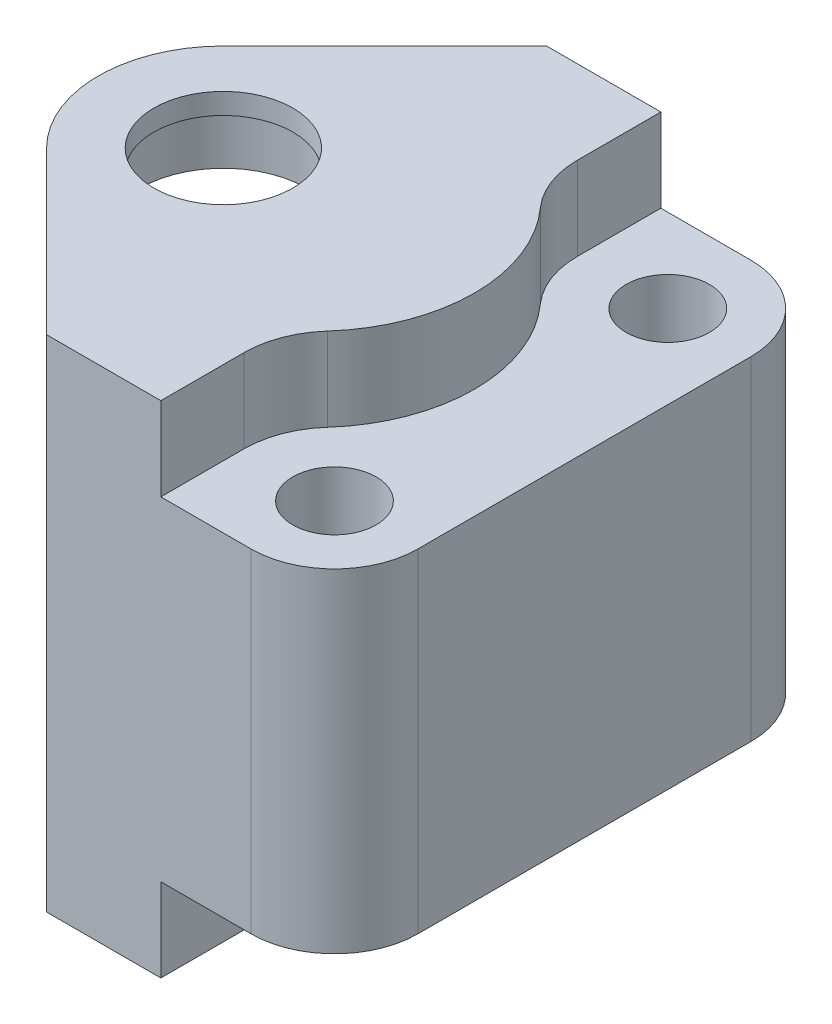
SolidWorks part; units mm, degrees
ref_plane "Front Plane" through (0, 0, 0) normal (0, 0, 1) x (1, 0, 0)
ref_plane "Top Plane" through (0, 0, 0) normal (0, 1, 0) x (1, 0, 0)
ref_plane "Right Plane" through (0, 0, 0) normal (1, 0, 0) x (0, 0, -1)
sketch "Sketch1" plane through (0, 0, 0) normal (0, 1, 0) x (1, 0, 0)
  line L1 (13, 6) -> (13, -6)
  line L2 (-8.0641, 0) -> (21.3803, 0) construction
  line L4 (-3.182, 3.182) -> (2.636, 9)
  line L5 (2.636, 9) -> (10, 9)
  line L6 (-3.182, -3.182) -> (2.636, -9)
  line L7 (2.636, -9) -> (10, -9)
  circle A1 centre (0, 0) radius 3 construction
  circle A2 centre (10, 6) radius 1.5
  circle A3 centre (10, -6) radius 1.5
  arc A4 (-3.182, -3.182) -> (-3.182, 3.182) centre (0, 0) cw
  arc A5 (10, 9) -> (13, 6) centre (10, 6) cw
  arc A6 (10, -9) -> (13, -6) centre (10, -6) ccw
  point P16 (13, 0)
  dimension "D1" = 12
  dimension "D2" = 6
  dimension "D3" = 3
  dimension "D4" = 4.5
  dimension "D5" = 3
  dimension "D6" = 10
  dimension "D7" = 18
  dimension "D8" = 90
extrude "Boss-Extrude1" add sketch "Sketch1" along normal mid plane 18
sketch "Sketch2" plane through (0, 0, 0) normal (0, 1, 0) x (1, 0, 0)
  line L0 (5.001, 1.5977) -> (2.636, 9)
  line L5 (2.636, -9) -> (5.001, -1.5977)
  line L6 (-3.182, -3.182) -> (2.636, -9) construction
  line L7 (2.636, 9) -> (-3.182, 3.182) construction
  line L8 (-3.182, -3.182) -> (2.636, -9)
  line L9 (2.636, 9) -> (-3.182, 3.182)
  arc A0 (5.001, 1.5977) -> (5.001, -1.5977) centre (0, 0) cw
  arc A2 (-3.182, 3.182) -> (-3.182, -3.182) centre (0, 0) ccw construction
  arc A3 (-3.182, 3.182) -> (-3.182, -3.182) centre (0, 0) ccw
  dimension "D2" = 5.25
extrude "Cut-Extrude1" cut sketch "Sketch2" along normal mid plane 12.5
sketch "Sketch3" plane through (0, 0, 0) normal (0, 0, 1) x (1, 0, 0)
  line L0 (0, -11.5038) -> (0, 11.5038) construction
  line L1 (-2.5, 9) -> (-2.5, 8.25)
  line L3 (-2.5, 8.25) -> (-3, 8.25)
  line L4 (-3, 8.25) -> (-3, 6.25)
  line L6 (-3, 6.25) -> (0, 6.25)
  line L7 (0, 6.25) -> (0, 9)
  line L8 (0, 9) -> (-2.5, 9)
  line L9 (6.0691, 0) -> (-6.0691, 0) construction
  line L10 (0, -6.25) -> (0, -9)
  line L11 (0, -9) -> (-2.5, -9)
  line L12 (-3, -6.25) -> (0, -6.25)
  line L13 (-3, -8.25) -> (-3, -6.25)
  line L14 (-2.5, -8.25) -> (-3, -8.25)
  line L15 (-2.5, -9) -> (-2.5, -8.25)
  line L16 (-3.182, 9) -> (2.636, 9) construction
  line L17 (-3.182, 6.25) -> (2.636, 6.25) construction
  point P4 (0, 0)
  point P18 (0, 0)
  dimension "D1" = 2
  dimension "D2" = 0.5
  dimension "D3" = 6
revolve "Cut-Revolve1" cut sketch "Sketch3" angle 360 about L0
sketch "Sketch4" plane through (0, 0, 0) normal (0, 1, 0) x (1, 0, 0)
  line L0 (0, 0) -> (14.4535, 0) construction
  line L1 (2.636, -9) -> (10, -9) construction
  line L2 (13, -6) -> (13, 6) construction
  line L3 (10, 9) -> (2.636, 9) construction
  line L4 (6.75, -9) -> (10, -9)
  line L5 (13, -6) -> (13, 6)
  line L6 (10, 9) -> (6.75, 9)
  line L7 (6.75, 6) -> (6.75, 9)
  line L8 (6.75, -6) -> (6.75, -9)
  arc A0 (6.75, 6) -> (7.5776, 3.8333) centre (10, 6) ccw
  arc A1 (7.5776, 3.8333) -> (7.5776, -3.8333) centre (3.2918, 0) cw
  arc A2 (7.5776, -3.8333) -> (6.75, -6) centre (10, -6) ccw
  arc A3 (10, -9) -> (13, -6) centre (10, -6) ccw construction
  arc A4 (13, 6) -> (10, 9) centre (10, 6) ccw construction
  arc A5 (10, -9) -> (13, -6) centre (10, -6) ccw
  arc A6 (13, 6) -> (10, 9) centre (10, 6) ccw
  point P3 (0, 0)
  dimension "D1" = 3.25
  dimension "D2" = 5.75
extrude "Cut-Extrude2" cut sketch "Sketch4" against normal blind 3 from surface starting at face at (0, 9, -2.5)
extrude "Cut-Extrude3" cut sketch "Sketch4<2>" along normal blind 3 from surface starting at face at (0, -9, -2.5)
sketch "Sketch4<2>" plane through (0, 0, 0) normal (0, 1, 0) x (1, 0, 0) same geometry as "Sketch4"
ref_axis "Axis1" through (0, 9.6175, 0) along (0, -1, 0)
